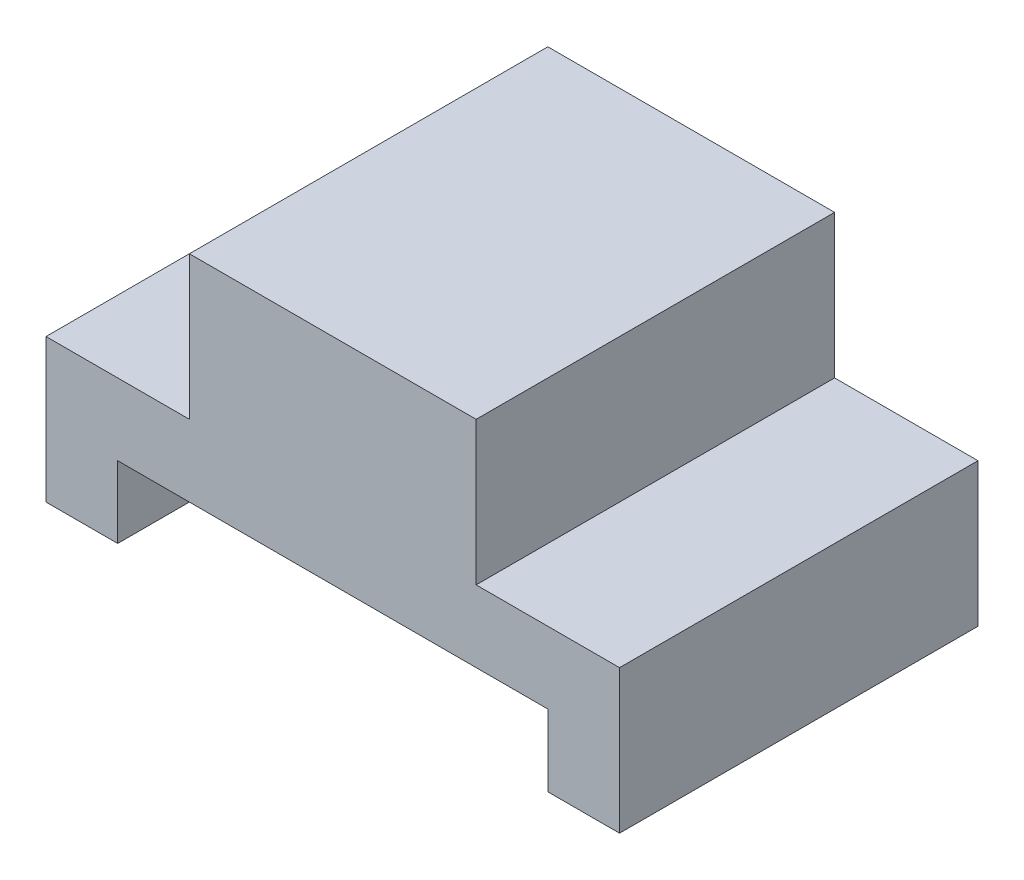
SolidWorks part; units mm, degrees
note: The reader was unsure of these and kept them because the rebuilt part matched: shared geometry of "Croquis4<2>".
ref_plane "Alzado" through (0, 0, 0) normal (0, 0, 1) x (1, 0, 0)
ref_plane "Planta" through (0, 0, 0) normal (0, 1, 0) x (1, 0, 0)
ref_plane "Vista lateral" through (0, 0, 0) normal (1, 0, 0) x (0, 0, -1)
sketch "Croquis2" plane through (0, 0, 0) normal (0, 1, 0) x (1, 0, 0)
  line L5 (-7950, -4800.5317) -> (50, -4800.5317)
  line L6 (-7950, -4800.5317) -> (-7950, 199.4683)
  line L7 (-7950, 199.4683) -> (50, 199.4683)
  line L8 (50, -4800.5317) -> (50, 199.4683)
  line L9 (-7950, -4800.5317) -> (50, 199.4683) construction
  line L10 (-7950, 199.4683) -> (50, -4800.5317) construction
  dimension "D1" = 8000
  dimension "D2" = 5000
extrude "Saliente-Extruir1" add sketch "Croquis2" along normal blind 1000
sketch "Croquis3" plane through (0, 1000, 0) normal (0, 1, 0) x (1, 0, 0)
  line L0 (50, 199.4683) -> (-7950, 199.4683) construction
  line L1 (-5950, 199.4683) -> (-1950, 199.4683)
  line L2 (-5950, 199.4683) -> (-5950, -4800.5317)
  line L3 (-5950, -4800.5317) -> (-1950, -4800.5317)
  line L4 (-1950, 199.4683) -> (-1950, -4800.5317)
  line L5 (-7950, -4800.5317) -> (50, -4800.5317) construction
  line L6 (-7950, 199.4683) -> (-7950, -4800.5317) construction
  dimension "D1" = 2000
  dimension "D2" = 4000
extrude "Saliente-Extruir2" add sketch "Croquis3" along normal blind 2000
sketch "Croquis4" plane through (0, 0, 0) normal (0, -1, 0) x (1, 0, 0)
  line L0 (-7950, 4800.5317) -> (50, 4800.5317) construction
  line L1 (-6950, 4800.5317) -> (-7950, 4800.5317)
  line L2 (-6950, 4800.5317) -> (-6950, -199.4683)
  line L3 (-6950, -199.4683) -> (-7950, -199.4683)
  line L4 (-7950, 4800.5317) -> (-7950, -199.4683)
  line L6 (50, -199.4683) -> (-7950, -199.4683) construction
  line L7 (-950, 4800.5317) -> (50, 4800.5317)
  line L8 (-950, 4800.5317) -> (-950, -199.4683)
  line L9 (-950, -199.4683) -> (50, -199.4683)
  line L10 (50, 4800.5317) -> (50, -199.4683)
  line L11 (50, 4800.5317) -> (50, -199.4683) construction
  dimension "D1" = 1000
  dimension "D2" = 1000
extrude "Saliente-Extruir4" add sketch "Croquis4<2>" along normal blind 1000
sketch "Croquis4<2>" plane through (0, 0, 0) normal (0, -1, 0) x (1, 0, 0) same geometry as "Croquis4"
extrude "Saliente-Extruir3" add sketch "Croquis4" along normal blind 1000
